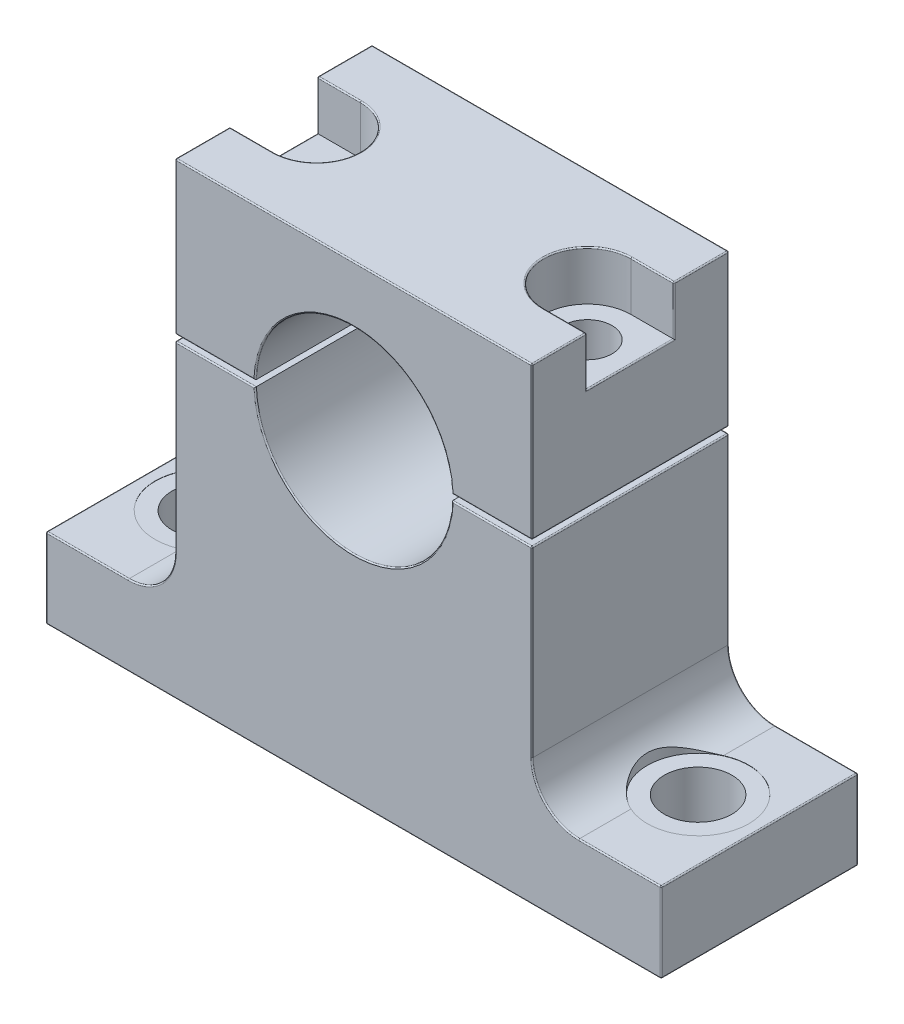
SolidWorks part; units mm, degrees
note: '?' marks a value the reader was unsure of.
material "ABS"
ref_plane "Front Plane" through (0, 0, 0) normal (0, 0, 1) x (1, 0, 0)
ref_plane "Top Plane" through (0, 0, 0) normal (0, 1, 0) x (1, 0, 0)
ref_plane "Right Plane" through (0, 0, 0) normal (1, 0, 0) x (0, 0, -1)
sketch "Sketch1" plane through (0, 0, 0) normal (0, 0, 1) x (1, 0, 0)
  line L0 (0, 12.6) -> (0, -25.4) construction
  line L1 (25, -25.4) -> (-25, -25.4) construction
  line L2 (-14.5, 12.6) -> (14.5, 12.6) construction
  line L3 (0, 0.25) -> (0, -0.25) construction
  line L4 (-11, 0) -> (11, 0) construction
  line L5 (-20, -18.9) -> (20, -18.9) construction
  line L6 (-11, 12.6) -> (-11, -25.4) construction
  line L7 (-14.5, 12.6) -> (-7.5, 12.6) construction
  line L8 (-13, -25.4) -> (-9, -25.4) construction
  line L9 (-22.75, -18.9) -> (-17.25, -18.9) construction
  line L10 (-24.125, -18.9) -> (-15.875, -18.9) construction
  circle A0 centre (0, 0) radius 8 construction
  point P7 (0, 0)
  point P8 (0, -25.4)
  point P11 (0, -18.9)
  point P14 (0, 12.6)
  point P15 (0, 0)
  point P20 (0, -18.9)
  point P23 (-11, 8.6)
  point P26 (-11, 12.6)
  point P27 (-11, -25.4)
  point P30 (-20, -18.9)
  point P35 (-20, -18.9)
  dimension "D1" = 0.5
  dimension "D3" = 4
  dimension "D4" = 8.25
sketch "Sketch2" plane through (0, 0, 0) normal (0, 0, 1) x (1, 0, 0)
  line L0 (-14.5, 12.6) -> (14.5, 12.6)
  line L1 (25, -25.4) -> (-25, -25.4) construction
  line L2 (25, -25.4) -> (-25, -25.4)
  line L3 (-25, -25.4) -> (-25, -18.9)
  line L4 (-25, -18.9) -> (-18.3, -18.9)
  line L5 (-14.5, -15.1) -> (-14.5, -0.25)
  line L6 (14.5, 12.6) -> (14.5, 0.25)
  line L7 (18.3, -18.9) -> (25, -18.9)
  line L8 (25, -18.9) -> (25, -25.4)
  line L9 (-14.5, 0.25) -> (-7.9961, 0.25)
  line L10 (-14.5, -0.25) -> (-7.9961, -0.25)
  line L11 (-14.5, 0.25) -> (-14.5, 12.6)
  line L12 (14.5, -0.25) -> (14.5, -15.1)
  line L13 (7.9961, 0.25) -> (14.5, 0.25)
  line L14 (7.9961, -0.25) -> (14.5, -0.25)
  circle A0 centre (0, 0) radius 8 construction
  arc A1 (-7.9961, -0.25) -> (7.9961, -0.25) centre (0, 0) ccw
  arc A2 (7.9961, 0.25) -> (-7.9961, 0.25) centre (0, 0) ccw
  arc A3 (14.5, -15.1) -> (18.3, -18.9) centre (18.3, -15.1) ccw
  arc A4 (-18.3, -18.9) -> (-14.5, -15.1) centre (-18.3, -15.1) ccw
  dimension "D1" = 3.8
extrude "Boss-Extrude1" add sketch "Sketch2" along normal mid plane 16
sketch "Sketch3" plane through (0, -18.9, 0) normal (0, 1, 0) x (1, 0, 0)
  line L0 (25, 0) -> (-25, 0) construction
  line L1 (-11, 0) -> (11, 0) construction
  circle A0 centre (-11, 0) radius 3.5
  circle A1 centre (11, 0) radius 3.5
  circle A2 centre (-20, 0) radius 2.75
  circle A3 centre (20, 0) radius 2.75
  circle A4 centre (-20, 0) radius 4.125 construction
  circle A5 centre (20, 0) radius 4.125 construction
  circle A6 centre (-11, 0) radius 3.5 construction
  circle A9 centre (11, 0) radius 3.5 construction
  point P6 (0, 0)
  point P16 (0, 0)
sketch "Sketch4" plane through (0, -18.9, 0) normal (0, 1, 0) x (1, 0, 0)
  circle A0 centre (-20, 0) radius 2.75 construction
  circle A1 centre (20, 0) radius 2.75 construction
  circle A2 centre (-20, 0) radius 2.75
  circle A3 centre (20, 0) radius 2.75
  point P0 (-20, 0)
extrude "Cut-Extrude1" cut sketch "Sketch4" against normal through all
sketch "Sketch5" plane through (0, -18.9, 0) normal (0, 1, 0) x (1, 0, 0)
  circle A0 centre (20, 0) radius 4.125 construction
  circle A1 centre (-20, 0) radius 4.125 construction
  circle A2 centre (20, 0) radius 4.125
  circle A3 centre (-20, 0) radius 4.125
extrude "Cut-Extrude2" cut sketch "Sketch5" against normal blind 0.02 and the other way through all
sketch "Sketch6" plane through (0, 12.6, 0) normal (0, 1, 0) x (1, 0, 0)
  circle A0 centre (11, 0) radius 3.5 construction
  circle A1 centre (-11, 0) radius 3.5 construction
  circle A2 centre (11, 0) radius 3.5 construction
  circle A3 centre (-11, 0) radius 3.5 construction
  circle A4 centre (-11, 0) radius 3.55
  circle A5 centre (11, 0) radius 3.55
  dimension "D1" = 0.05
extrude "Cut-Extrude3" cut sketch "Sketch6" against normal up to vertex (4 mm away) up to point (-11, 8.6, 0)
sketch "Sketch12" plane through (0, 12.6, 0) normal (0, 1, 0) x (1, 0, 0)
  line L0 (-11, 3.55) -> (-14.5, 3.55)
  line L1 (-14.5, -8) -> (-14.5, -0.5937) construction
  line L2 (-14.5, 3.55) -> (-14.5, -3.55)
  line L3 (-14.5, -8) -> (-14.5, 8) construction
  line L4 (-14.5, -3.55) -> (-11, -3.55)
  line L5 (0, 8) -> (0, -8) construction
  line L6 (14.5, 8) -> (-14.5, 8) construction
  line L7 (14.5, -8) -> (-14.5, -8) construction
  line L8 (14.5, -3.55) -> (11, -3.55)
  line L9 (14.5, 3.55) -> (14.5, -3.55)
  line L10 (11, 3.55) -> (14.5, 3.55)
  arc A1 (-11, -3.55) -> (-11, 3.55) centre (-11, 0) ccw
  arc A2 (11, -3.55) -> (11, 3.55) centre (11, 0) cw
  circle A4 centre (-11, 0) radius 3.55 construction
extrude "Cut-Extrude6" cut sketch "Sketch12" against normal up to vertex (4 mm away) up to point (-11, 8.6, 0)
sketch "Sketch8" plane through (0, 12.6, 0) normal (0, 1, 0) x (1, 0, 0)
  circle A2 centre (11, 0) radius 2
  circle A3 centre (-11, 0) radius 2
extrude "Cut-Extrude4" cut sketch "Sketch8" against normal through all
sketch "Sketch10" plane through (0, 0, 0) normal (0, 0, 1) x (1, 0, 0)
  line L4 (-11, 12.6) -> (-7.5, 12.6)
  line L5 (-7.5, 12.6) -> (-7.5, 8.6)
  line L6 (-7.5, 8.6) -> (-9, 8.6)
  line L7 (-9, 8.6) -> (-9, -25.4)
  line L10 (-9, -25.4) -> (-11, -25.4)
  line L11 (-11, -25.4) -> (-11, 12.6)
revolve "Revolve1" [suppressed] add sketch "Sketch10" angle 360 about L11
sketch "Sketch11" [suppressed] plane through (0, 12.6, 0) normal (0, 1, 0) x (1, 0, 0)
  line L0 (-11, 0) -> (-11, 1.75) construction
  line L1 (-11, 1.75) -> (-12.5155, 0.875)
  line L2 (-12.5155, 0.875) -> (-12.5155, -0.875)
  line L3 (-12.5155, -0.875) -> (-11, -1.75)
  line L4 (-11, -1.75) -> (-9.4845, -0.875)
  line L5 (-9.4845, -0.875) -> (-9.4845, 0.875)
  line L6 (-9.4845, 0.875) -> (-11, 1.75)
  line L7 (-11, 3.5) -> (-11, 1.75) construction
  circle A0 centre (-11, 0) radius 1.5155 construction
  circle A2 centre (-11, 0) radius 3.5 construction
  circle A3 centre (-11, 0) radius 3.5 construction
  dimension "D1" = 7
extrude "Cut-Extrude5" [suppressed] cut sketch "Sketch11" against normal blind 3
chamfer "Chamfer1" [suppressed] distance 0.6 angle 45
mirror "Mirror1" [suppressed] about plane through (0, 0, 0) normal (1, 0, 0)
fillet "Fillet1" radius 0.1 30 edges at (21.65, -18.9, -8) (15.613, -17.787, -8) (11.248, -0.25, -8) (0, -8, -8) (-11.248, -0.25, -8) (-15.613, -17.787, -8) (-21.65, -18.9, -8) (0, -25.4, -8) (14.5, -0.25, 0) (14.5, -7.675, -8) (25, -18.9, 0) (25, -22.15, -8) (25, -25.4, 0) (-25, -18.9, 0) (-25, -25.4, 0) (-25, -22.15, -8) (-14.5, -0.25, 0) (-14.5, -7.675, -8) (0, -25.4, 8) (-25, -22.15, 8) (-21.65, -18.9, 8) (-15.613, -17.787, 8) (-14.5, -7.675, 8) (-11.248, -0.25, 8) (0, -8, 8) (11.248, -0.25, 8) (14.5, -7.675, 8) (15.613, -17.787, 8) (21.65, -18.9, 8) (25, -22.15, 8)
fillet "Fillet2" radius 0.1 30 edges at (14.5, 0.25, 0) (-14.5, 0.25, 0) (-11.248, 0.25, -8) (0, 8, -8) (11.248, 0.25, -8) (14.5, 6.425, -8) (-14.5, 6.425, -8) (-14.5, 12.6, 5.775) (-14.5, 12.6, -5.775) (0, 12.6, -8) (14.5, 12.6, -5.775) (14.5, 12.6, 5.775) (0, 12.6, 8) (14.5, 6.425, 8) (11.248, 0.25, 8) (0, 8, 8) (-11.248, 0.25, 8) (-14.5, 6.425, 8) (-12.75, 12.6, -3.55) (12.75, 12.6, -3.55) (12.75, 12.6, 3.55) (-12.75, 12.6, 3.55) (14.5, 10.6, 3.55) (14.5, 10.6, -3.55) (-14.5, 10.6, 3.55) (-14.5, 10.6, -3.55) (14.5, 8.6, 0) (-14.5, 8.6, 0) (-7.45, 12.6, 0) (7.45, 12.6, 0)
ref_plane "Contact Plane 1" through (0, -25.4, 0) normal (0, -1, 0) x (-1, 0, 0)
ref_axis "Center Axis 1" through (0, 0, 7.9) along (0, 0, -1)?
split "Split1" trim tools "Top Plane" bodies to split 109 128 resulting bodies 130 131
equation "\"D3@Sketch1\"=\"G@Sketch1\""
equation "\"D4@Sketch1\"=\"K@Sketch1\"*1.5"
equation "\"D1@Sketch2\"=\"Height@Sketch1\"*.1"
